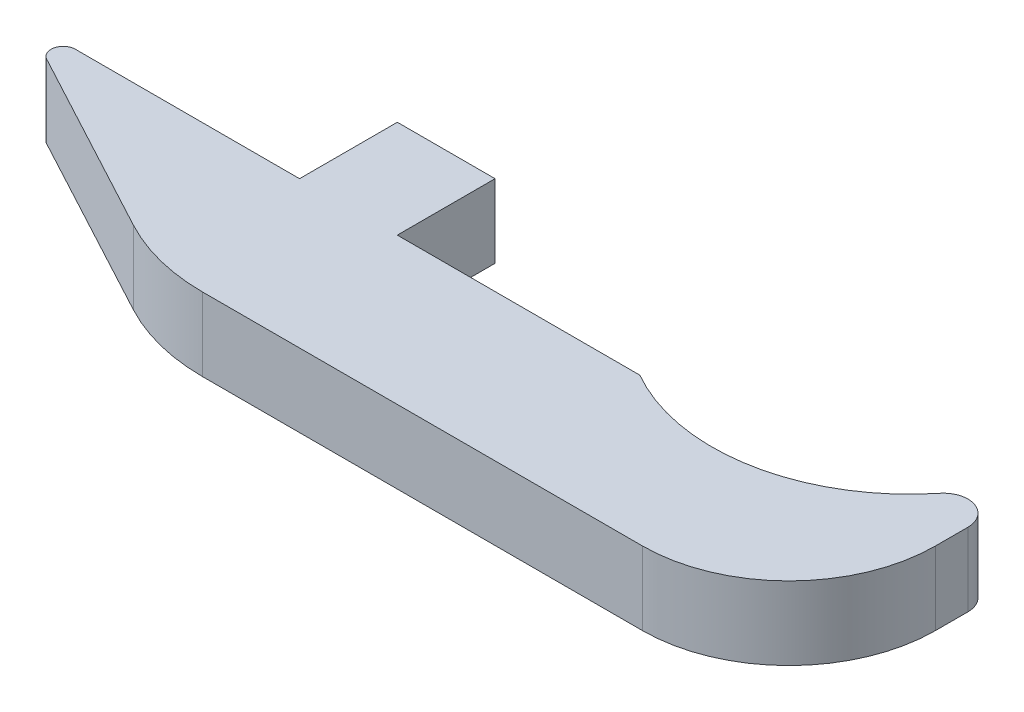
SolidWorks part; units mm, degrees
material "AISI 4130 Steel, annealed at 865C"
ref_plane "X-Y Datum" through (0, 0, 0) normal (0, 0, 1) x (1, 0, 0)
ref_plane "X-Z Datum" through (0, 0, 0) normal (0, 1, 0) x (1, 0, 0)
ref_plane "Y-Z Datum" through (0, 0, 0) normal (1, 0, 0) x (0, 0, -1)
sketch "Sketch1" plane through (0, 0, 0) normal (0, 1, 0) x (1, 0, 0)
  line L0 (20.8895, 0) -> (0, 0) construction
  line L1 (49.3776, 0) -> (0, 0)
  line L2 (49.3776, 0) -> (49.3776, 11.1252)
  line L3 (20.9296, -9.525) -> (62.2046, -9.525)
  line L4 (62.2046, 11.1252) -> (62.2046, -9.525)
  line L5 (3.175, 0) -> (20.9296, -9.525)
  circle A0 centre (49.3776, 11.1252) radius 12.827
  dimension "D3" = 25.654
  dimension "D5" = 9.525
  dimension "D1" = 49.3776
  dimension "D2" = 11.1252
  dimension "D4" = 3.175
  dimension "D6" = 41.275
extrude "Boss-Extrude1" add sketch "Sketch1" along normal blind 4.7625 contours L1 A0 region at (37.4995, 0, 4.291)
fillet "Fillet1" radius 9.525 1 edges at (62.2046, 2.3813, 9.525)
fillet "Fillet2" radius 1.5875 1 edges at (62.2046, 2.3813, -11.1252)
fillet "Fillet4" radius 12.7 1 edges at (20.9296, 2.3813, 9.525)
sketch "Sketch2" plane through (0, 0, 0) normal (0, -1, 0) x (1, 0, 0)
  line L1 (27.2395, -6.35) -> (27.2395, 0)
  line L2 (-7.0505, -6.35) -> (25.8501, -6.35) construction
  line L3 (27.2395, 0) -> (20.8895, 0)
  line L4 (27.2395, 0) -> (27.2395, -6.35)
  line L5 (27.2395, -6.35) -> (20.8895, -6.35)
  line L6 (20.8895, 0) -> (20.8895, -6.35)
  line L7 (33.5895, 0) -> (33.5895, -6.35) construction
  line M6 (3.175, 0) -> (42.9931, 0)
  dimension "D1" = 6.35
  dimension "D2" = 6.35
extrude "Boss-Extrude2" add sketch "Sketch2" against normal blind 4.7625 contours L6 L5 L1 M6 region at (24.0645, 0, -3.175)
fillet "Fillet5" radius 0.7937 1 edges at (3.175, 2.3813, 0)
